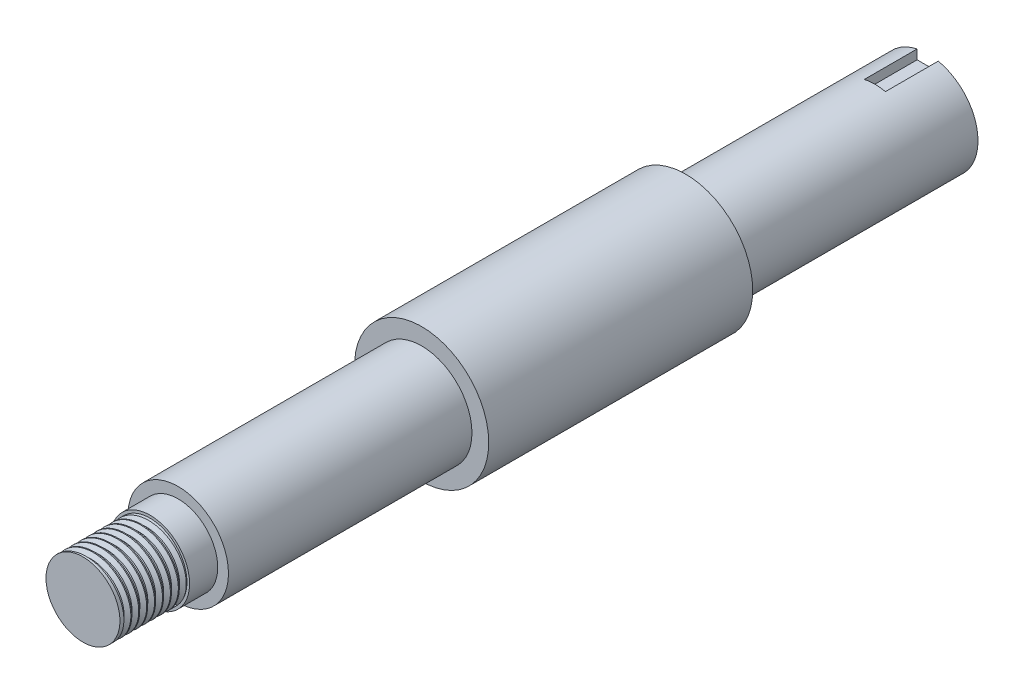
SolidWorks part; units mm, degrees
material "AISI 1020"
ref_plane "Front Plane" through (0, 0, 0) normal (0, 0, 1) x (1, 0, 0)
ref_plane "Top Plane" through (0, 0, 0) normal (0, 1, 0) x (1, 0, 0)
ref_plane "Right Plane" through (0, 0, 0) normal (1, 0, 0) x (0, 0, -1)
sketch "Sketch Spindle Skeleton" plane through (0, 0, 0) normal (1, 0, 0) x (0, 0, -1)
  line L0 (-95.847, -9.525) -> (-141.966, -9.525)
  line L5 (-1000, 0) -> (49000, 0)
  line L6 (0, -9.525) -> (0, 9.525)
  line L13 (0, 9.525) -> (-45.847, 9.525)
  line L26 (-45.847, 9.525) -> (-45.847, 12.7)
  line L27 (-45.847, 12.7) -> (-95.847, 12.7)
  line L32 (-95.847, 12.7) -> (-95.847, 9.525)
  line L34 (-160, 7) -> (-160, -7)
  line L36 (-95.847, -9.525) -> (-95.847, -12.7)
  line L37 (-95.847, -12.7) -> (-45.847, -12.7)
  line L38 (-45.847, -12.7) -> (-45.847, -9.525)
  line L39 (0, -9.525) -> (-45.847, -9.525)
  line L40 (-25.305, 36.322) -> (-16.305, 36.322)
  line L41 (-111.341, 22.6187) -> (-95.847, 22.6187)
  line L42 (-111.341, 22.6187) -> (-111.341, -22.6187)
  line L43 (-111.341, -22.6187) -> (-95.847, -22.6187)
  line L44 (-95.847, 22.6187) -> (-95.847, -22.6187)
  line L45 (-111.341, 22.6187) -> (-95.847, -22.6187) construction
  line L46 (-111.341, -22.6187) -> (-95.847, 22.6187) construction
  line L47 (-30.353, 22.6187) -> (-45.847, 22.6187)
  line L48 (-30.353, 22.6187) -> (-30.353, -22.6187)
  line L49 (-30.353, -22.6187) -> (-45.847, -22.6187)
  line L50 (-45.847, 22.6187) -> (-45.847, -22.6187)
  line L51 (-30.353, 22.6187) -> (-45.847, -22.6187) construction
  line L52 (-30.353, -22.6187) -> (-45.847, 22.6187) construction
  line L59 (-16.305, 36.322) -> (-16.305, -36.322)
  line L60 (-16.305, -36.322) -> (-25.305, -36.322)
  line L61 (-25.305, -22.6187) -> (-27.305, -22.6187)
  line L62 (-27.305, -22.6187) -> (-27.305, -12.5)
  line L63 (-27.305, -12.5) -> (-25.305, -12.5)
  line L64 (-25.305, -12.5) -> (-25.305, 12.5)
  line L65 (-25.305, 12.5) -> (-27.305, 12.5)
  line L66 (-27.305, 12.5) -> (-27.305, 22.6187)
  line L67 (-27.305, 22.6187) -> (-25.305, 22.6187)
  line L68 (-25.305, 22.6187) -> (-25.305, 36.322)
  line L69 (-25.305, -22.6187) -> (-25.305, -36.322)
  line L71 (-119.469, 36.322) -> (-26.305, 36.322)
  line L72 (-119.469, 36.322) -> (-119.469, -36.322)
  line L73 (-119.469, -36.322) -> (-26.305, -36.322)
  line L74 (-26.305, 36.322) -> (-26.305, -36.322)
  line L75 (-119.469, 36.322) -> (-26.305, -36.322) construction
  line L76 (-119.469, -36.322) -> (-26.305, 36.322) construction
  line L78 (-147.3, -7) -> (-160, -7)
  line L79 (-95.847, 9.525) -> (-141.966, 9.525)
  line L80 (-147.3, 7) -> (-160, 7)
  line L82 (-118.9065, 9.525) -> (-118.9065, -9.525) construction
  line L83 (-22.9235, 9.525) -> (-22.9235, -9.525) construction
  line L96 (-119.469, 36.322) -> (-134.709, 36.322)
  line L98 (-119.469, -36.322) -> (-134.709, -36.322)
  line L99 (-134.709, 36.322) -> (-134.709, -36.322)
  line L110 (-119.469, 36.322) -> (-119.469, -36.322)
  line L111 (-147.3, 7) -> (-147.3, 7.493)
  line L112 (-147.3, 7.493) -> (-141.966, 7.493)
  line L113 (-141.966, 7.493) -> (-141.966, 9.525)
  line L114 (-141.966, -9.525) -> (-141.966, -7.493)
  line L115 (-141.966, -7.493) -> (-147.3, -7.493)
  line L116 (-147.3, -7.493) -> (-147.3, -7)
  point P3 (0, 0)
  point P18 (-103.594, 0)
  point P24 (-38.1, 0)
  point P29 (-72.887, 0)
  point P48 (-16.305, 30.4704)
  point P60 (-16.305, 30.4704)
  point P70 (-134.709, 31.75)
revolve "Revolve Spindle" add sketch "Sketch Spindle Skeleton" angle 360 about L5
thread "Chuck Thread" pitch 1.5 start angle 0, offset 0, length 11.43, pitch 1.5, diameter 14
ref_plane "Plane2" through (-7, 0, 160) normal (0, -1, 0) x (-1, 0, 0)
sketch "Thread Profile2" plane through (-7, 0, 160) normal (0, -1, 0) x (-1, 0, 0)
  line L0 (0, 0) -> (0, 1.5) construction
  line L11 (0, 0) -> (0, 1.3125)
  line L12 (0, 1.3125) -> (-0.8119, 0.8437)
  line L13 (-0.8119, 0.8437) -> (-0.8119, 0.4687)
  line L15 (-0.8119, 0.4687) -> (0, 0)
  line L17 (-0.8119, 0.6562) -> (0, 0.6562) construction
  point P2 (0, 0)
  dimension "Pitch" = 1.5
  dimension "Profile_Angle" = 60
  dimension "Profile_Land" = 0.375
  dimension "Profile_Height" = 0.8119
sketch "Sketch Key" plane through (0, 0, 0) normal (0, 0, -1) x (-1, 0, 0)
  line L0 (0, 8.525) -> (0, 0) construction
  line L1 (-2, 7.525) -> (2, 7.525)
  line L2 (-2, 7.525) -> (-2, 9.525)
  line L3 (-2, 9.525) -> (2, 9.525)
  line L4 (2, 7.525) -> (2, 9.525)
  line L5 (-2, 7.525) -> (2, 9.525) construction
  line L6 (-2, 9.525) -> (2, 7.525) construction
  circle A1 centre (0, 0) radius 9.525
  circle A2 centre (0, 0) radius 9.525
  point P0 (0, 8.525)
  dimension "D2" = 4
  dimension "D3" = 2
  dimension "D1" = 0
extrude "Key Cut" cut sketch "Sketch Key" against normal blind 10 contours L3 L4 L1 L2
